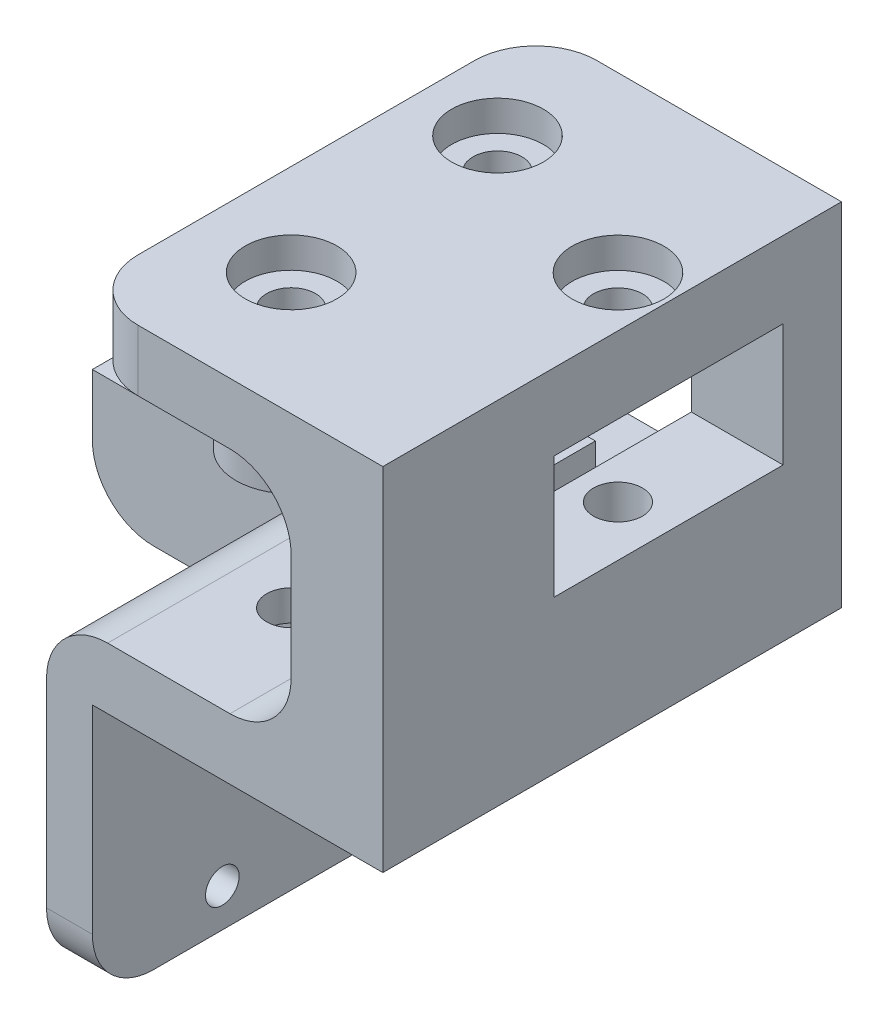
SolidWorks part; units mm, degrees
ref_plane "Plano frontal" through (0, 0, 0) normal (0, 0, 1) x (1, 0, 0)
ref_plane "Plano superior" through (0, 0, 0) normal (0, 1, 0) x (1, 0, 0)
ref_plane "Plano direito" through (0, 0, 0) normal (1, 0, 0) x (0, 0, -1)
sketch "Esboço1" plane through (0, 0, 0) normal (0, 0, 1) x (1, 0, 0)
  line L0 (0, 0) -> (3, 0)
  line L3 (15, 21) -> (-13, 21)
  line L4 (-13, 21) -> (-13, 36)
  line L5 (-13, 36) -> (1, 36)
  line L6 (1, 36) -> (1, 40)
  line L7 (1, 40) -> (-19, 40)
  line L9 (-19, 17) -> (0, 17)
  line L10 (0, 17) -> (0, 0)
  line L12 (15, 21) -> (15, 13)
  line L13 (3, 0) -> (3, 8)
  line L14 (15, 13) -> (31.662, 13) construction
  line L16 (-19, 17) -> (-19, 40)
  line L19 (8, 13) -> (15, 13)
  arc A0 (3, 8) -> (8, 13) centre (8, 8) cw
  dimension "D10" = 5
  dimension "D1" = 3
  dimension "D2" = 17
  dimension "D3" = 15
  dimension "D4" = 4
  dimension "D5" = 6
  dimension "D6" = 19
  dimension "D7" = 1
  dimension "D8" = 8
  dimension "D9" = 4
  dimension "D12" = 15
extrude "Ressalto-extrusão1" add sketch "Esboço1" along normal blind 30
sketch "Esboço3" plane through (0, 0, 0) normal (1, 0, 0) x (0, 0, -1)
  line L0 (0, 8.5) -> (-30, 8.5) construction
  line L1 (0, 17) -> (0, 0) construction
  line L2 (-30, 17) -> (-30, 0) construction
  line L4 (-30, 0) -> (0, 0) construction
  line L5 (-15, 0) -> (-15, 15) construction
  circle A0 centre (-8.5, 14.5) radius 1.1
  circle A4 centre (-21.5, 14.5) radius 1.1
  circle A5 centre (-8.5, 2.5) radius 1.1
  circle A6 centre (-21.5, 2.5) radius 1.1
  dimension "D3" = 2.2
  dimension "D1" = 12
  dimension "D2" = 13
extrude "Corte-extrusão1" cut sketch "Esboço3" against normal through all both and the other way through all
sketch "Esboço4" plane through (0, 0, 0) normal (0, 1, 0) x (1, 0, 0)
  line L0 (15, -15) -> (3, -15)
  line L1 (15, -30) -> (15, 0) construction
  line L2 (3, -30) -> (3, 0) construction
  line L3 (3, -15) -> (3, -30)
  line L4 (15, -15) -> (15, -30)
  line L5 (15, -30) -> (3, -30)
  line L6 (15, 0) -> (-13, 0) construction
  dimension "D1" = 15
extrude "Corte-extrusão6" cut sketch "Esboço4" against normal through all and the other way through all
sketch "Esboço5" plane through (0, 40, 0) normal (0, 1, 0) x (1, 0, 0)
  line L0 (1, -30) -> (-19, -30) construction
  line L1 (15, -15) -> (15, 0) construction
  line L2 (15, -15) -> (15, 0) construction
  circle A0 centre (-5, -22) radius 1.6
  circle A1 centre (-15.7, -11.32) radius 1.6
  circle A2 centre (-5, -22) radius 4.84 construction
  circle A3 centre (-15.7, -11.32) radius 4.84 construction
  circle A4 centre (11, -7.5) radius 1.6
  point P15 (15, -7.5)
  dimension "D2" = 3.2
  dimension "D5" = 9.68
  dimension "D6" = 1
  dimension "D1" = 8
  dimension "D3" = 5
  dimension "D4" = 15.7
  dimension "D7" = 4
extrude "Corte-extrusão7" cut sketch "Esboço5" against normal through all
sketch "Esboço7" plane through (0, 21, 0) normal (0, 1, 0) x (1, 0, 0)
  line L1 (-23.2, -3.82) -> (-8.2, -3.82)
  line L2 (-23.2, -3.82) -> (-23.2, -18.82)
  line L3 (-23.2, -18.82) -> (-8.2, -18.82)
  line L4 (-8.2, -3.82) -> (-8.2, -18.82)
  circle A0 centre (-15.7, -11.32) radius 7.5 construction
  dimension "D1" = 15
extrude "Corte-extrusão9" cut sketch "Esboço7" along normal offset from surface (8 mm away) 1 from offset 6 up to face at (-5, 36, 23.6)
sketch "Esboço9" plane through (0, 40, 0) normal (0, 1, 0) x (1, 0, 0)
  line L0 (1, -30) -> (1, 0) construction
  circle A1 centre (-4, -7.5) radius 1.6
  point P6 (11, -7.5)
  dimension "D1" = 3.2
  dimension "D3" = 5
extrude "Corte-extrusão11" cut sketch "Esboço9" against normal up to next
sketch "Esboço8" plane through (0, 40, 0) normal (0, 1, 0) x (1, 0, 0)
  circle A0 centre (-15.7, -11.32) radius 3
  circle A1 centre (-5, -22) radius 3
  circle A3 centre (-4, -7.5) radius 3
  circle A4 centre (-4, -7.5) radius 1.6 construction
  dimension "D1" = 6
extrude "Corte-extrusão10" cut sketch "Esboço8" against normal blind 2
sketch "Esboço14" plane through (0, 17, 0) normal (0, -1, 0) x (1, 0, 0)
  line L0 (11, 11) -> (15, 11)
  line L1 (-5, 25.2332) -> (-7.8, 23.6166)
  line L2 (-7.8, 23.6166) -> (-7.8, 20.3834)
  line L3 (-7.8, 20.3834) -> (-5, 18.7668)
  line L4 (-5, 18.7668) -> (-2.2, 20.3834)
  line L5 (-2.2, 20.3834) -> (-2.2, 23.6166)
  line L6 (-2.2, 23.6166) -> (-5, 25.2332)
  line L7 (-15.7, 14.5532) -> (-18.5, 12.9366)
  line L8 (-18.5, 12.9366) -> (-18.5, 9.7034)
  line L9 (-18.5, 9.7034) -> (-15.7, 8.0868)
  line L10 (-15.7, 8.0868) -> (-12.9, 9.7034)
  line L11 (-12.9, 9.7034) -> (-12.9, 12.9366)
  line L12 (-12.9, 12.9366) -> (-15.7, 14.5532)
  line L13 (15, 11) -> (15, 4)
  line L14 (15, 15) -> (15, 0) construction
  line L15 (15, 4) -> (11, 4)
  circle A0 centre (-5, 22) radius 2.8 construction
  circle A1 centre (-15.7, 11.32) radius 2.8 construction
  arc A2 (11, 11) -> (11, 4) centre (11, 7.5) ccw
  dimension "D1" = 5.6
  dimension "D2" = 7
extrude "Corte-extrusão14" cut sketch "Esboço14" against normal blind 2 and the other way through all
sketch "Esboço15" plane through (3, 0, 0) normal (1, 0, 0) x (0, 0, -1)
  circle A0 centre (-21.5, 14.5) radius 2.1
  circle A1 centre (-8.5, 14.5) radius 2.1
  circle A2 centre (-8.5, 2.5) radius 2.1
  circle A3 centre (-21.5, 2.5) radius 2.1
  dimension "D1" = 4.2
extrude "Corte-extrusão16" cut sketch "Esboço15" against normal offset from surface 2 and the other way through all up to face at (0, 15.6, 21.5)
fillet "Filete1" radius 4 9 edges at (1.5, 0, 0) (1.5, 0, 30) (3, 21, 22.5) (1, 38, 0) (-13, 21, 15) (15, 13, 2) (15, 13, 13) (1, 38, 30) (-13, 36, 15)
sketch "Esboço16" plane through (0, 21, 0) normal (0, 1, 0) x (1, 0, 0)
  line L0 (15, 0) -> (-9, 0) construction
  line L1 (-19, -3.82) -> (-9, -3.82)
  line L2 (-19, -3.82) -> (-19, 0)
  line L3 (-19, 0) -> (-9, 0)
  line L4 (-9, -3.82) -> (-9, 0)
  line L5 (-19, -30) -> (-19, 0) construction
  line L6 (15, 0) -> (-9, 0) construction
  line L7 (-13, -3.82) -> (-11.6458, -3.82) construction
  dimension "D1" = 4
extrude "Ressalto-extrusão2" add sketch "Esboço16" along normal blind 2
sketch "Esboço17" plane through (0, 21, 0) normal (0, 1, 0) x (1, 0, 0)
  line L0 (-9, -3.82) -> (-9, 0) construction
  line L1 (-9, -6.1) -> (6.9, -6.1)
  line L2 (-9, -6.1) -> (-9, -8.9)
  line L3 (-9, -8.9) -> (6.9, -8.9)
  line L4 (6.9, -6.1) -> (6.9, -8.9)
  line L5 (-9, -6.1) -> (6.9, -8.9) construction
  line L6 (-9, -8.9) -> (6.9, -6.1) construction
  circle A0 centre (11, -7.5) radius 1.6 construction
  point P0 (-1.05, -7.5)
  point P5 (11, -7.5)
  dimension "D1" = 2.5
  dimension "D2" = 2.8
extrude "Ressalto-extrusão3" add sketch "Esboço17" along normal blind 3.5
mirror "Espelhar1" about plane through (15, 21, 30) normal (-1, 0, 0) of bodies 114
sketch "Esboço18" plane through (-19, 0, 0) normal (-1, 0, 0) x (0, 0, 1)
  line L1 (-11.4252, 46.4499) -> (40.8237, 46.4499)
  line L2 (-11.4252, 46.4499) -> (-11.4252, -7.8633)
  line L3 (-11.4252, -7.8633) -> (40.8237, -7.8633)
  line L4 (40.8237, 46.4499) -> (40.8237, -7.8633)
  line L5 (-11.4252, 46.4499) -> (40.8237, -7.8633) construction
  line L6 (-11.4252, -7.8633) -> (40.8237, 46.4499) construction
  point P0 (14.6992, 19.2933)
extrude "Corte-extrusão17" cut sketch "Esboço18" against normal up to vertex (34 mm away) up to point (15, 17, 15)
sketch "Esboço19" plane through (0, 36, 0) normal (0, -1, 0) x (1, 0, 0)
  circle A0 centre (35, 22) radius 3.6
  circle A1 centre (35, 22) radius 1.6 construction
  circle A2 centre (35, 22) radius 1.6
  dimension "D1" = 2
extrude "Ressalto-extrusão4" add sketch "Esboço19" along normal blind 6
